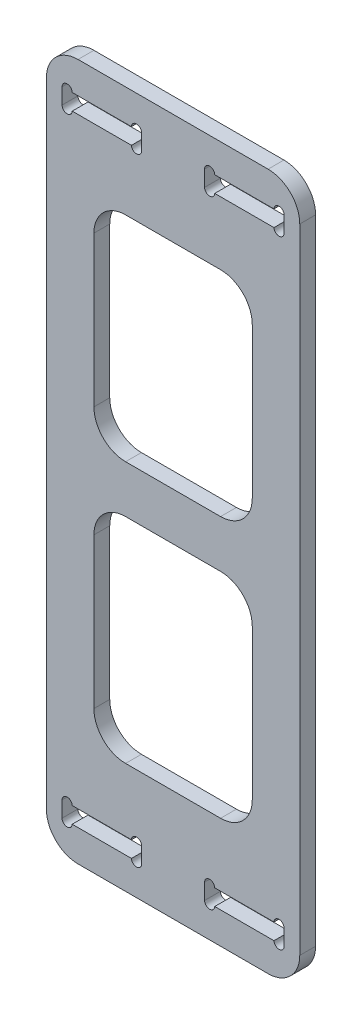
SolidWorks part; units mm, degrees
ref_plane "前视基准面" through (0, 0, 0) normal (0, 0, 1) x (1, 0, 0)
ref_plane "上视基准面" through (0, 0, 0) normal (0, 1, 0) x (1, 0, 0)
ref_plane "右视基准面" through (0, 0, 0) normal (1, 0, 0) x (0, 0, -1)
other "Configuration Table"
sketch "草图1" plane through (0, 0, 0) normal (0, 0, 1) x (1, 0, 0)
  line L0 (0, -5) -> (0, -15)
  line L1 (0, 0) -> (70, 0)
  line L2 (0, 0) -> (0, 190)
  line L3 (0, 190) -> (70, 190)
  line L4 (70, 0) -> (70, 190)
  line L5 (45, 0) -> (70, 0)
  line L6 (45, 0) -> (45, -5)
  line L7 (45, -5) -> (70, -5)
  line L8 (70, 0) -> (70, -5)
  line L9 (0, 0) -> (25, 0)
  line L10 (0, 0) -> (0, -5)
  line L11 (0, -5) -> (25, -5)
  line L12 (25, 0) -> (25, -5)
  line L13 (70, 190) -> (45, 190)
  line L14 (70, 190) -> (70, 195)
  line L15 (70, 195) -> (45, 195)
  line L16 (45, 190) -> (45, 195)
  line L17 (0, 190) -> (25, 190)
  line L18 (0, 190) -> (0, 195)
  line L19 (0, 195) -> (25, 195)
  line L20 (25, 190) -> (25, 195)
  line L21 (0, -15) -> (70, -15)
  line L22 (70, -15) -> (70, -5)
  line L23 (0, 195) -> (0, 205)
  line L24 (0, 205) -> (70, 205)
  line L25 (70, 205) -> (70, 195)
  dimension "D1" = 70
  dimension "D2" = 190
  dimension "D3" = 25
  dimension "D4" = 25
  dimension "D5" = 5
  dimension "D6" = 5
  dimension "D7" = 25
  dimension "D8" = 25
  dimension "D9" = 5
  dimension "D10" = 5
  dimension "D11" = 10
  dimension "D12" = 10
extrude "凸台-拉伸1" add sketch "草图1" along normal blind 5 contours L16 L3 L14 L15 | L1 L4 L3 L2 | L3 L20 L19 L18 | L8 L1 L6 L7 | L12 L1 L10 L11 | L21 L22 L7 L6 L1 L12 L11 L0 | L25 L24 L23 L19 L20 L3 L16 L15 region at (35, -9.0625, 0) region at (12.5, -2.5, 0) region at (35, 95, 0) region at (12.5, 192.5, 0) region at (57.5, -2.5, 0) region at (35, 199.0625, 0) region at (57.5, 192.5, 0)
sketch "草图3" plane through (0, 0, 5) normal (0, 0, 1) x (1, 0, 0)
  line L0 (-18.3476, 95) -> (112.3639, 95) construction
  line L1 (35, -9.6754) -> (35, 200.1889) construction
  line L2 (70, -15) -> (70, 205) construction
  line L3 (0, -15) -> (0, 205) construction
  line L7 (10, 87.5) -> (60, 87.5)
  line L8 (10, 87.5) -> (10, 20)
  line L9 (10, 20) -> (60, 20)
  line L10 (60, 87.5) -> (60, 20)
  line L11 (10, 170) -> (60, 170)
  line L12 (10, 102.5) -> (60, 102.5)
  line L13 (10, 102.5) -> (10, 170)
  line L14 (60, 102.5) -> (60, 170)
  line L15 (0, 205) -> (70, 205) construction
  line L16 (0, -15) -> (70, -15) construction
  dimension "D1" = 15
  dimension "D2" = 10
  dimension "D3" = 10
  dimension "D4" = 35
extrude "切除-拉伸2" cut sketch "草图3" against normal up to surface (5 mm away) up to face at (35, 95, 0)
fillet "圆角1" radius 10 8 edges at (10, 20, 2.5) (60, 20, 2.5) (60, 87.5, 2.5) (10, 87.5, 2.5) (10, 102.5, 2.5) (60, 102.5, 2.5) (10, 170, 2.5) (60, 170, 2.5)
sketch "草图5" plane through (0, 0, 5) normal (0, 0, 1) x (1, 0, 0)
  line L0 (35, 216.361) -> (35, -30.6918) construction
  line L1 (70, -15) -> (70, 205) construction
  line L2 (0, -15) -> (0, 205) construction
  line L3 (0, -15) -> (70, -15) construction
  line L4 (3.1, 0) -> (21.9, 0)
  line L5 (0, 0) -> (0, -5)
  line L6 (3.1, -5) -> (21.9, -5)
  line L7 (25, 0) -> (25, -5)
  line L8 (45, 0) -> (45, -5)
  line L9 (66.9, -5) -> (48.1, -5)
  line L10 (70, 0) -> (70, -5)
  line L11 (66.9, 0) -> (48.1, 0)
  line L12 (-69.2147, 95) -> (137.572, 95) construction
  line L13 (0, 205) -> (70, 205) construction
  line L14 (66.9, 190) -> (48.1, 190)
  line L15 (70, 190) -> (70, 195)
  line L16 (66.9, 195) -> (48.1, 195)
  line L17 (45, 190) -> (45, 195)
  line L18 (25, 190) -> (25, 195)
  line L19 (3.1, 195) -> (21.9, 195)
  line L20 (0, 190) -> (0, 195)
  line L21 (3.1, 190) -> (21.9, 190)
  arc A0 (3.1, 0) -> (0, 0) centre (1.55, 0) ccw
  arc A1 (25, 0) -> (21.9, 0) centre (23.45, 0) ccw
  arc A2 (21.9, -5) -> (25, -5) centre (23.45, -5) ccw
  arc A3 (0, -5) -> (3.1, -5) centre (1.55, -5) ccw
  arc A4 (70, -5) -> (66.9, -5) centre (68.45, -5) cw
  arc A5 (48.1, -5) -> (45, -5) centre (46.55, -5) cw
  arc A6 (45, 0) -> (48.1, 0) centre (46.55, 0) cw
  arc A7 (66.9, 0) -> (70, 0) centre (68.45, 0) cw
  arc A8 (66.9, 190) -> (70, 190) centre (68.45, 190) ccw
  arc A9 (45, 190) -> (48.1, 190) centre (46.55, 190) ccw
  arc A10 (48.1, 195) -> (45, 195) centre (46.55, 195) ccw
  arc A11 (70, 195) -> (66.9, 195) centre (68.45, 195) ccw
  arc A12 (0, 195) -> (3.1, 195) centre (1.55, 195) cw
  arc A13 (21.9, 195) -> (25, 195) centre (23.45, 195) cw
  arc A14 (25, 190) -> (21.9, 190) centre (23.45, 190) cw
  arc A15 (3.1, 190) -> (0, 190) centre (1.55, 190) cw
  dimension "D5" = 3.1
  dimension "D1" = 95
  dimension "D2" = 5
  dimension "D3" = 25
  dimension "D4" = 35
extrude "切除-拉伸3" cut sketch "草图5" against normal blind 10
sketch "草图6" plane through (0, 0, 5) normal (0, 0, 1) x (1, 0, 0)
  line L0 (0, -15) -> (70, -15) construction
  line L1 (70, 205) -> (75, 205)
  line L2 (70, 205) -> (70, -15)
  line L3 (70, -15) -> (75, -15)
  line L4 (75, 205) -> (75, -15)
  line L6 (0, 205) -> (-5, 205)
  line L7 (0, 205) -> (0, -15)
  line L8 (0, -15) -> (-5, -15)
  line L9 (-5, 205) -> (-5, -15)
  dimension "D1" = 5
  dimension "D2" = 5
extrude "凸台-拉伸2" add sketch "草图6" against normal up to surface (5 mm away) up to face at (35, 53.75, 0)
other "移动面1" flip direction yes face at (70, -2.5, 2.5) face at (68.45, -5.775, 2.5) face at (68.45, 0.775, 2.5) face at (57.5, 0, 2.5) face at (57.5, -5, 2.5) face at (46.55, -5.775, 2.5) face at (46.55, 0.775, 2.5) face at (45, -2.5, 2.5) face at (25, -2.5, 2.5) face at (23.45, -5.775, 2.5) face at (23.45, 0.775, 2.5) face at (12.5, -5, 2.5) face at (12.5, 0, 2.5) face at (1.55, 0.775, 2.5) face at (1.55, -5.775, 2.5) face at (0, -2.5, 2.5) face at (1.55, 189.225, 2.5) face at (1.55, 195.775, 2.5) face at (0, 192.5, 2.5) face at (12.5, 195, 2.5) face at (12.5, 190, 2.5) face at (23.45, 189.225, 2.5) face at (25, 192.5, 2.5) face at (23.45, 195.775, 2.5) face at (68.45, 189.225, 2.5) face at (70, 192.5, 2.5) face at (57.5, 190, 2.5) face at (46.55, 189.225, 2.5) face at (45, 192.5, 2.5) face at (46.55, 195.775, 2.5) face at (57.5, 195, 2.5) face at (68.45, 195.775, 2.5) offset 0.05 parameters "D1"=0.05
fillet "圆角2" radius 10 4 edges at (75, 205, 2.5) (-5, 205, 2.5) (-5, -15, 2.5) (75, -15, 2.5)
